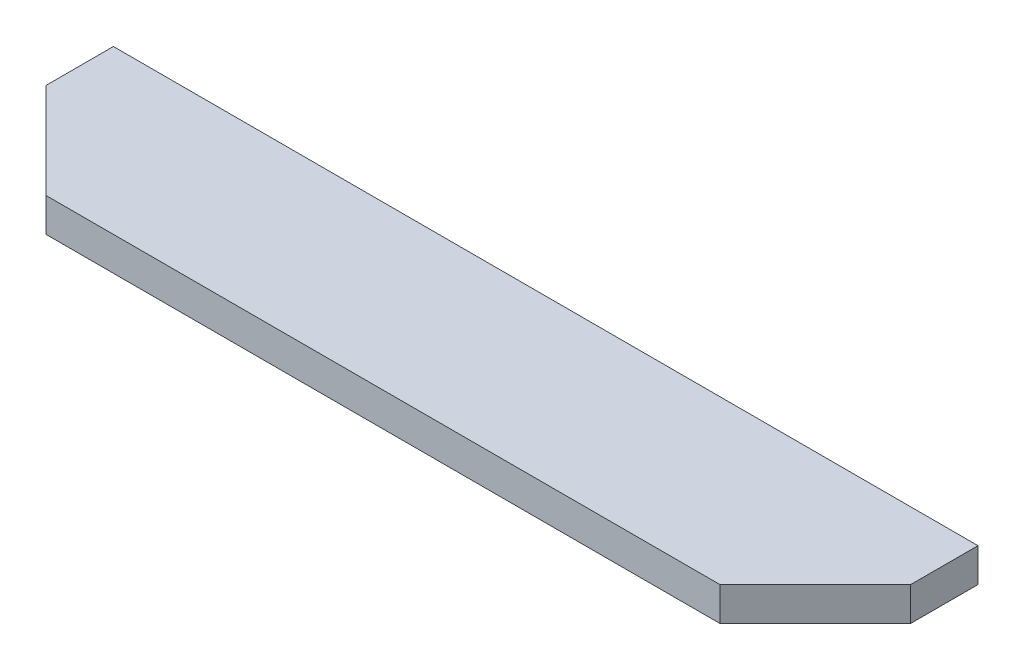
SolidWorks part; units mm, degrees
material "Pure Gold"
ref_plane "Front Plane" through (0, 0, 0) normal (0, 0, 1) x (1, 0, 0)
ref_plane "Top Plane" through (0, 0, 0) normal (0, 1, 0) x (1, 0, 0)
ref_plane "Right Plane" through (0, 0, 0) normal (1, 0, 0) x (0, 0, -1)
sketch "Sketch2" plane through (0, 0, 0) normal (0, 1, 0) x (1, 0, 0)
  line L0 (0, 0) -> (-100, 0)
  line L1 (-100, 0) -> (-114.1421, 14.1421)
  line L2 (-114.1421, 14.1421) -> (-114.1421, 24.1421)
  line L3 (0, 0) -> (14.1421, 14.1421)
  line L4 (14.1421, 14.1421) -> (14.1421, 24.1421)
  line L5 (14.1421, 24.1421) -> (-114.1421, 24.1421)
  dimension "D1" = 100
  dimension "D2" = 20
  dimension "D3" = 10
  dimension "D4" = 20
  dimension "D5" = 10
extrude "Boss-Extrude1" add sketch "Sketch2" along normal blind 5
